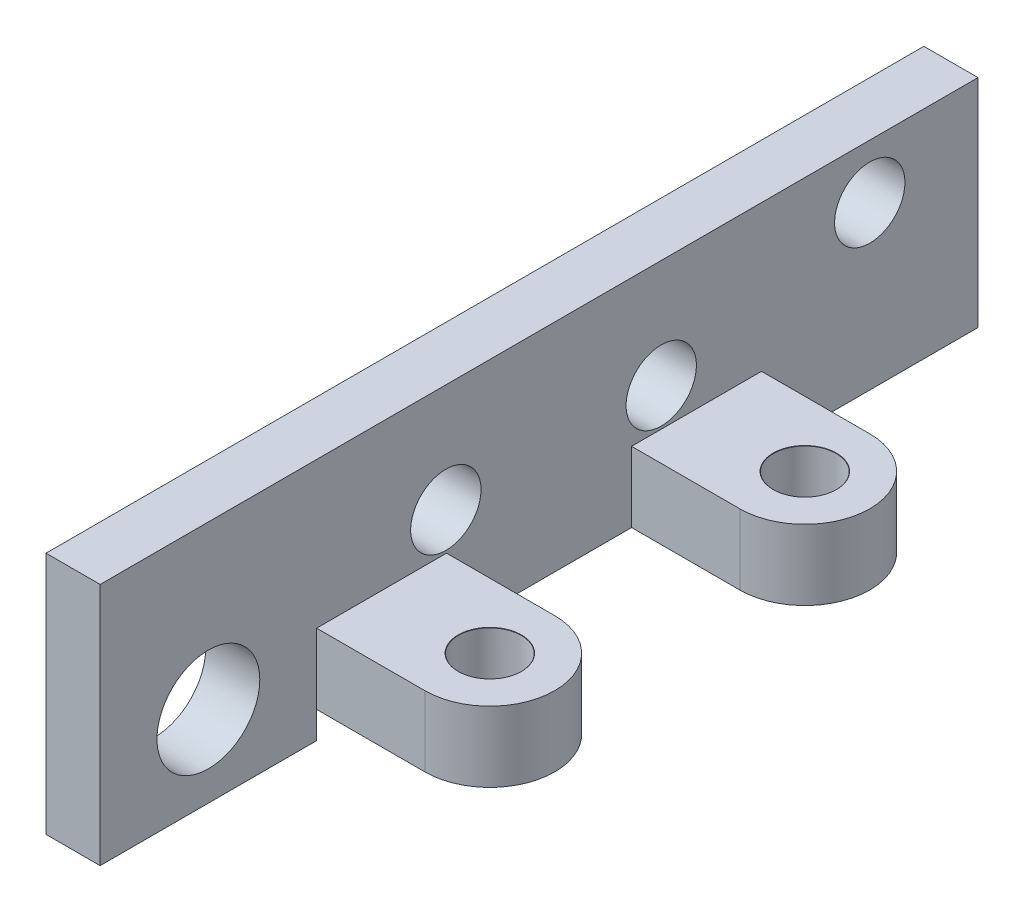
SolidWorks part; units mm, degrees
ref_plane "Front Plane" through (0, 0, 0) normal (0, 0, 1) x (1, 0, 0)
ref_plane "Top Plane" through (0, 0, 0) normal (0, 1, 0) x (1, 0, 0)
ref_plane "Right Plane" through (0, 0, 0) normal (1, 0, 0) x (0, 0, -1)
sketch "Sketch1" plane through (0, 0, 0) normal (1, 0, 0) x (0, 0, -1)
  line L0 (-81.099, 0) -> (-81.099, -2.5)
  line L1 (0, 0) -> (-81.099, 0)
  line L2 (0, 0) -> (0, 20)
  line L3 (0, 20) -> (-81.099, 20)
  line L4 (-81.099, 0) -> (-81.099, 20)
  line L5 (-81.099, -2.5) -> (-71.099, -2.5)
  line L6 (-71.099, -2.5) -> (-61.099, -2.5)
  line L7 (-61.099, -2.5) -> (-61.099, 0)
  circle A0 centre (-29.2616, 10) radius 3.25
  circle A1 centre (-49.1616, 10) radius 3.25
  circle A2 centre (-71.099, 5) radius 4.75
  circle A5 centre (-10, 15) radius 3.25
  point P11 (0, 0)
  dimension "D3" = 6.5
  dimension "D4" = 10
  dimension "D10" = 9.5
  dimension "D12" = 10
  dimension "D6" = 19.9
  dimension "D2" = 20
  dimension "D5" = 22.5
  dimension "D7" = 5
  dimension "D8" = 5
  dimension "D9" = 19.9
  dimension "D11" = 2.5
  dimension "D13" = 10
extrude "Boss-Extrude1" add sketch "Sketch1" along normal blind 5 contours L4 L1 L2 L3 A5 A2 A1 A0 | L6 L7 L1 L0 L5 region at (0, -1.25, 71.099) region at (0, 10.1299, 39.8173)
sketch "Sketch2" plane through (5, 0, 0) normal (1, 0, 0) x (0, 0, -1)
  line L0 (0, 0) -> (-40.5495, 0) construction
  line L1 (0, 0) -> (-61.099, 0) construction
  line L2 (-81.099, -2.5) -> (-81.099, 20) construction
  line L3 (-40.5495, 0) -> (-40.5495, 20) construction
  line L6 (-61.099, 0) -> (-49.099, 0)
  line L7 (-61.099, 0) -> (-61.099, 6.5)
  line L8 (-61.099, 6.5) -> (-49.099, 6.5)
  line L9 (-49.099, 6.5) -> (-49.099, 0)
  line L10 (-40.5495, 0) -> (-81.099, 0) construction
  line L11 (0, 20) -> (-81.099, 20) construction
  line L12 (-20, 6.5) -> (-32, 6.5)
  line L15 (-20, 0) -> (-20, 6.5)
  line L16 (-20, 0) -> (-32, 0)
  line L17 (-32, 6.5) -> (-32, 0)
  dimension "D5" = 12
  dimension "D6" = 6.5
extrude "Boss-Extrude2" add sketch "Sketch2" along normal blind 10 contours L9 L6 L7 L8 | L12 L17 L16 L15
sketch "Sketch3" plane through (0, 6.5, 0) normal (0, 1, 0) x (1, 0, 0)
  line L0 (15, -49.099) -> (15, -61.099)
  arc A0 (15, -49.099) -> (15, -61.099) centre (15, -55.099) cw
  circle A1 centre (15, -55.099) radius 2.5
  dimension "D1" = 5
extrude "Boss-Extrude3" add sketch "Sketch3" against normal up to surface (6.5 mm away) contours A0 L0 up to face at (7.7273, 0, 35.045)
hole_wizard "M5 Clearance Hole1" positions "3DSketch1" profile "Sketch4" hole size "M5" standard "ANSI Metric" end condition through all
sketch3d "3DSketch1"
  point P0 (15, 6.5, 55.099)
sketch "Sketch4" plane through (15, 6.5, 55.099) normal (1, 0, 0) x (0, 0, 1)
  line L0 (0, 0) -> (0, 9)
  line L1 (0, 9) -> (2.9, 9)
  line L2 (2.9, 9) -> (2.9, 0.025)
  line L3 (2.9, 0.025) -> (2.925, 0)
  line L5 (2.925, 0) -> (0, 0)
  line L6 (-2.9, 0.025) -> (-2.925, 0) construction
  line L11 (0, -6.35) -> (0, 107.95) construction
  dimension "Thru Hole Dia." = 5.8
  dimension "Thru Hole Depth" = 9
  dimension "Near C'Sink Dia." = 5.85
  dimension "Near C'Sink Angle" = 90
ref_plane "Plane1" through (0, 0, 40.5495) normal (0, 0, 1) x (1, 0, 0)
mirror "Mirror1" about plane through (0, 0, 40.5495) normal (0, 0, 1) of "Boss-Extrude3", "M5 Clearance Hole1"
